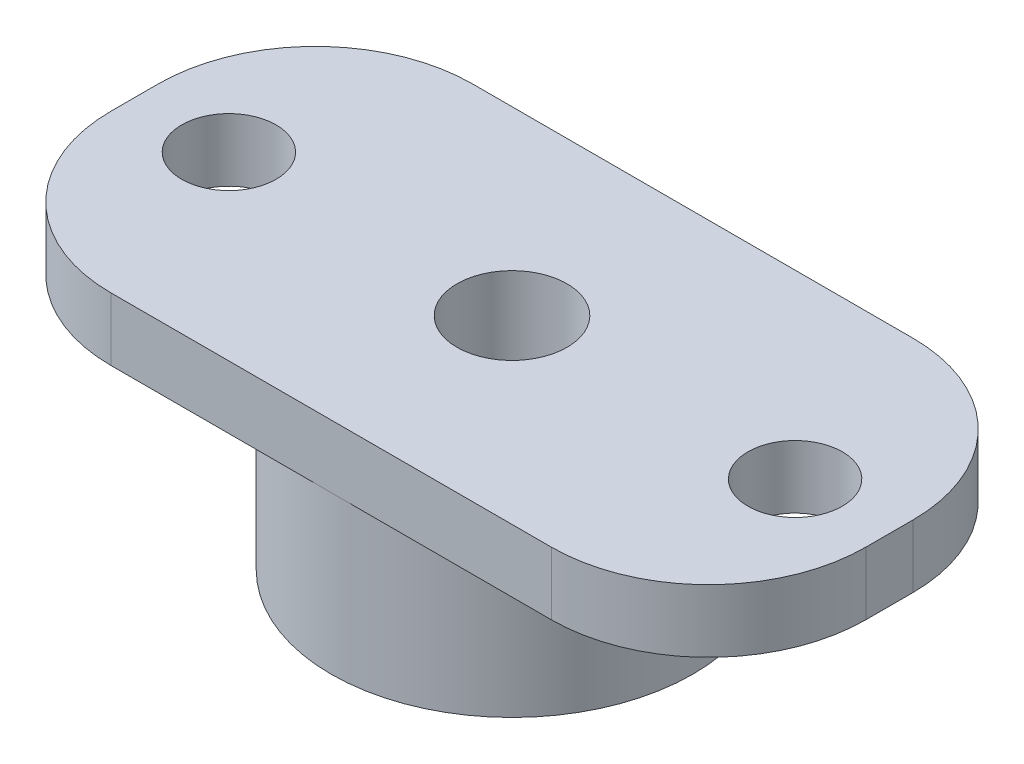
SolidWorks part; units mm, degrees
ref_plane "前视基准面" through (0, 0, 0) normal (0, 0, 1) x (1, 0, 0)
ref_plane "上视基准面" through (0, 0, 0) normal (0, 1, 0) x (1, 0, 0)
ref_plane "右视基准面" through (0, 0, 0) normal (1, 0, 0) x (0, 0, -1)
other "Configuration Table"
sketch "草图1" plane through (0, 0, 0) normal (0, 1, 0) x (1, 0, 0)
  line L9 (-12, 5.75) -> (12, 5.75)
  line L10 (-12, 5.75) -> (-12, -5.75)
  line L11 (-12, -5.75) -> (12, -5.75)
  line L12 (12, 5.75) -> (12, -5.75)
  circle A0 centre (0, 0) radius 1.75
  circle A1 centre (0, 0) radius 5.75
  circle A2 centre (0, 0) radius 3.1
  point P0 (0, 0)
  point P10 (0, -5.75)
  dimension "D1" = 4
  dimension "D2" = 6.2
  dimension "D3" = 3.5
  dimension "D4" = 24
extrude "凸台-拉伸1" add sketch "草图1" along normal blind 7 contours A1 | A0
extrude "切除-拉伸1" cut sketch "草图1<20>" along normal blind 2.6 contours A2
sketch "草图1<20>" plane through (0, 0, 0) normal (0, 1, 0) x (1, 0, 0) same geometry as "草图1"
extrude "凸台-拉伸2" add sketch "草图1<21>" against normal blind 2 from surface contours L10 L11 L12 L9 | A0 starting at face at (0, 7, 5.75)
sketch "草图1<21>" plane through (0, 0, 0) normal (0, 1, 0) x (1, 0, 0) same geometry as "草图1"
sketch "草图2" plane through (0, 5, 0) normal (0, -1, 0) x (1, 0, 0)
  line L0 (9, 0) -> (-9, 0)
  line L1 (12, 5.75) -> (12, -5.75) construction
  circle A0 centre (-9, 0) radius 1.5
  circle A1 centre (9, 0) radius 1.5
  point P4 (7.1227, 0)
  dimension "D1" = 3
  dimension "D2" = 3
extrude "切除-拉伸2" cut sketch "草图2" against normal through all contours A0 | A1
fillet "圆角1" radius 5 4 edges at (-12, 6, -5.75) (-12, 6, 5.75) (12, 6, -5.75) (12, 6, 5.75)
